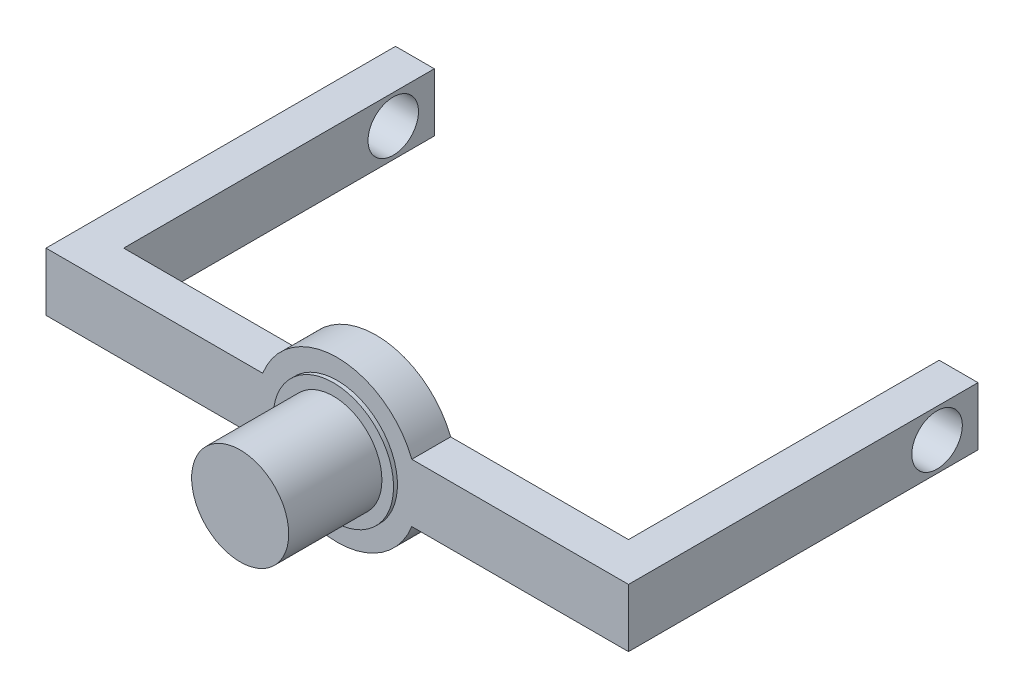
SolidWorks part; units mm, degrees
ref_plane "Płaszczyzna przednia" through (0, 0, 0) normal (0, 0, 1) x (1, 0, 0)
ref_plane "Płaszczyzna górna" through (0, 0, 0) normal (0, 1, 0) x (1, 0, 0)
ref_plane "Płaszczyzna prawa" through (0, 0, 0) normal (1, 0, 0) x (0, 0, -1)
sketch "Szkic1" plane through (0, 0, 0) normal (0, 0, 1) x (1, 0, 0)
  line L1 (-75, -7.5) -> (75, -7.5)
  line L2 (-75, -7.5) -> (-75, 7.5)
  line L3 (-75, 7.5) -> (75, 7.5)
  line L4 (75, -7.5) -> (75, 7.5)
  line L5 (-75, -7.5) -> (75, 7.5) construction
  line L6 (-75, 7.5) -> (75, -7.5) construction
  point P0 (0, 0)
  dimension "D1" = 150
  dimension "D2" = 15
extrude "Dodanie-wyciągnięcie1" add sketch "Szkic1" along normal blind 10
sketch "Szkic2" plane through (0, 0, 10) normal (0, 0, 1) x (1, 0, 0)
  circle A0 centre (0, 0) radius 20.6112
extrude "Dodanie-wyciągnięcie2" add sketch "Szkic2" against normal blind 10
sketch "Szkic3" plane through (0, 0, 10) normal (0, 0, 1) x (1, 0, 0)
  circle A0 centre (0, 0) radius 12.5
  dimension "D1" = 25
sketch "Szkic4" plane through (0, 0, 0) normal (0, 0, -1) x (-1, 0, 0)
  line L0 (19.1982, 7.5) -> (75, 7.5) construction
  line L1 (75, -7.5) -> (65, -7.5)
  line L2 (75, -7.5) -> (75, 7.5)
  line L3 (75, 7.5) -> (65, 7.5)
  line L4 (65, -7.5) -> (65, 7.5)
  dimension "D1" = 10
extrude "Dodanie-wyciągnięcie3" add sketch "Szkic4" along normal blind 80
sketch "Szkic5" plane through (-65, 0, 0) normal (1, 0, 0) x (0, 0, -1)
  circle A0 centre (69.42, 0) radius 6.5
  dimension "D1" = 13
extrude "Wytnij-wyciągnięcie2" cut sketch "Szkic5" against normal blind 80
sketch "Szkic6" plane through (0, 0, 0) normal (0, 0, -1) x (-1, 0, 0)
  line L0 (-75, 7.5) -> (-19.1982, 7.5) construction
  line L1 (-75, -7.5) -> (-65, -7.5)
  line L2 (-75, -7.5) -> (-75, 7.5)
  line L3 (-75, 7.5) -> (-65, 7.5)
  line L4 (-65, -7.5) -> (-65, 7.5)
  dimension "D1" = 10
extrude "Dodanie-wyciągnięcie4" add sketch "Szkic6" along normal blind 80
sketch "Szkic7" plane through (65, 0, 0) normal (-1, 0, 0) x (0, 0, 1)
  circle A0 centre (-69.4591, 0) radius 6.5
  dimension "D1" = 13
extrude "Wytnij-wyciągnięcie3" cut sketch "Szkic7" against normal blind 80
extrude "Dodanie-wyciągnięcie5" add sketch "Szkic3" along normal blind 25 contours A0
sketch "Szkic8" plane through (0, 0, 10) normal (0, 0, 1) x (1, 0, 0)
  circle A0 centre (0, 0) radius 15.5
  dimension "D1" = 31
extrude "Dodanie-wyciągnięcie6" add sketch "Szkic8" along normal blind 1
